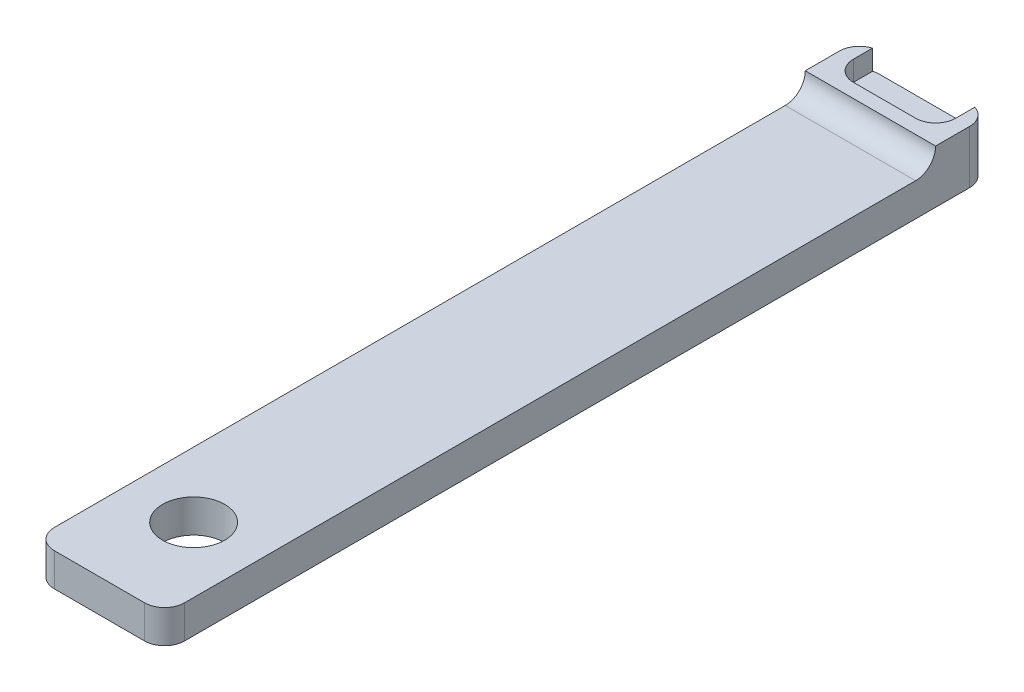
SolidWorks part; units mm, degrees
ref_plane "Front Plane" through (0, 0, 0) normal (0, 0, 1) x (1, 0, 0)
ref_plane "Top Plane" through (0, 0, 0) normal (0, 1, 0) x (1, 0, 0)
ref_plane "Right Plane" through (0, 0, 0) normal (1, 0, 0) x (0, 0, -1)
sketch "Sketch1" plane through (0, 0, 0) normal (0, 1, 0) x (1, 0, 0)
  line L0 (3.25, 0) -> (3.25, 4.7) construction
  line L1 (0, 0) -> (6.5, 0)
  line L2 (0, 0) -> (0, 41.15)
  line L3 (0, 41.15) -> (6.5, 41.15)
  line L4 (6.5, 0) -> (6.5, 41.15)
  circle A0 centre (3.25, 4.7) radius 1.55
  dimension "D2" = 3.1
  dimension "D1" = 6.5
  dimension "D3" = 4.7
  dimension "D4" = 41.15
extrude "Boss-Extrude1" add sketch "Sketch1" along normal blind 1.65
sketch "Sketch2" plane through (0, 1.65, 0) normal (0, 1, 0) x (1, 0, 0)
  line L0 (0.7, 39.15) -> (5.8, 39.15) construction
  line L1 (0, 41.15) -> (0.7, 41.15)
  line L2 (0, 41.15) -> (0, 39.15)
  line L3 (0, 39.15) -> (0.7, 39.15) construction
  line L4 (0.7, 41.15) -> (0.7, 39.15)
  line L5 (6.5, 41.15) -> (5.8, 41.15)
  line L6 (6.5, 41.15) -> (6.5, 39.15)
  line L7 (6.5, 39.15) -> (5.8, 39.15) construction
  line L8 (5.8, 41.15) -> (5.8, 39.15)
  line L9 (6.5, 0) -> (6.5, 41.15) construction
  line L10 (0.7, 39.15) -> (5.8, 39.15)
  line L11 (0, 39.15) -> (0, 38.45)
  line L12 (0, 38.45) -> (6.5, 38.45)
  line L13 (6.5, 39.15) -> (6.5, 38.45)
  line L14 (0, 39.15) -> (0.7, 39.15) construction
  line L15 (5.8, 39.15) -> (6.5, 39.15) construction
  dimension "D1" = 5.1
  dimension "D2" = 2
  dimension "D3" = 0.7
extrude "Boss-Extrude2" add sketch "Sketch2" along normal blind 1
fillet "Fillet1" radius 1 7 edges at (6.5, 1.325, -41.15) (0, 1.325, -41.15) (6.5, 0.825, 0) (0, 0.825, 0) (3.25, 1.65, -38.45) (0.7, 2.15, -39.15) (5.8, 2.15, -39.15)
